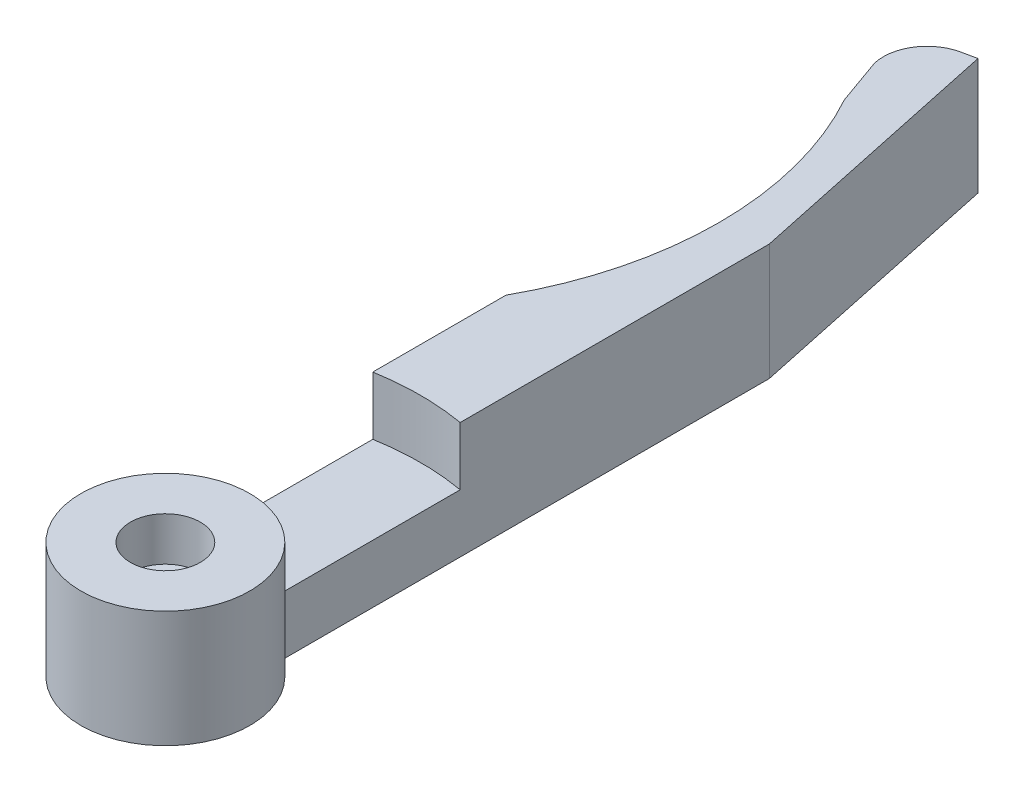
SolidWorks part; units mm, degrees
ref_plane "Plan de face" through (0, 0, 0) normal (0, 0, 1) x (1, 0, 0)
ref_plane "Plan de dessus" through (0, 0, 0) normal (0, 1, 0) x (1, 0, 0)
ref_plane "Plan de droite" through (0, 0, 0) normal (1, 0, 0) x (0, 0, -1)
sketch "Esquisse1" plane through (0, 0, 0) normal (0, 1, 0) x (1, 0, 0)
  line L0 (-3, 50.619) -> (-3, 49.619) construction
  line L1 (2, 55.619) -> (3, 55.619) construction
  line L2 (-3, 55.619) -> (-3, 4.9639) construction
  line L3 (-3, 4.9639) -> (3, 4.9639) construction
  line L4 (3, 55.619) -> (3, 4.9639) construction
  line L5 (-3, 26.381) -> (-3, 4.9639)
  line L7 (-3, 4.9639) -> (3, 4.9639) construction
  line L12 (0, 4.9639) -> (0, -14.5149) construction
  line L13 (-4.1404, 52.822) -> (-3, 49.619)
  line L14 (-1.8453, 56.4495) -> (-0.8672, 56.6574)
  line L15 (-0.8672, 56.6574) -> (3, 38.4639)
  line L16 (3, 38.4639) -> (3, 4.9639)
  arc A0 (-3, 49.619) -> (-3, 26.381) centre (-24, 38) cw
  arc A1 (2, 55.619) -> (-3, 50.619) centre (2, 50.619) ccw construction
  circle A2 centre (0, 0) radius 2.4 construction
  arc A3 (-4.1404, 52.822) -> (-1.8453, 56.4495) centre (-1.2216, 53.5151) cw
  arc A4 (-3, 4.9639) -> (3, 4.9639) centre (0, 0) ccw
  point P19 (0, 38)
  point P25 (-4.3024, 55.9871)
  dimension "D2" = 24
  dimension "D5" = 5
  dimension "D10" = 3
  dimension "D7" = 4.8
  dimension "D11" = 5.8
  dimension "D1" = 6
  dimension "D3" = 21
  dimension "D4" = 6
  dimension "D6" = 38
  dimension "D8" = 3.5
  dimension "D9" = 6.5
  dimension "D12" = 33.5
  dimension "D13" = 12
  dimension "D14" = 18.6
  dimension "D15" = 3.4
  dimension "D16" = 1
extrude "Boss.-Extru.1" add sketch "Esquisse1" along normal blind 8
sketch "Esquisse2" plane through (0, 8, 0) normal (0, 1, 0) x (1, 0, 0)
  line L0 (0, 38) -> (0, 0) construction
  circle A0 centre (0, 0) radius 2.4
  arc A1 (-3, 26.381) -> (-3, 49.619) centre (-24, 38) ccw construction
  dimension "D2" = 4.8
  dimension "D1" = 38
extrude "Enlèv. mat.-Extru.1" cut sketch "Esquisse2" against normal blind 3
sketch "Esquisse3" plane through (0, 5, 0) normal (0, 1, 0) x (1, 0, 0)
  circle A0 centre (0, 0) radius 1.25
  dimension "D1" = 2.5
extrude "Enlèv. mat.-Extru.2" cut sketch "Esquisse3" against normal up to next
sketch "Esquisse4" plane through (0, 0, 0) normal (0, -1, 0) x (1, 0, 0)
  circle A0 centre (0, 0) radius 3
  dimension "D1" = 6
extrude "Enlèv. mat.-Extru.3" cut sketch "Esquisse4" against normal blind 2
sketch "Esquisse5" plane through (0, 8, 0) normal (0, 1, 0) x (1, 0, 0)
  line L0 (-3, 4.9639) -> (-3, 17.2409)
  line L1 (3, 4.9639) -> (3, 17.2409)
  line L2 (3, 4.9639) -> (3, 38.4639) construction
  circle A0 centre (0, 0) radius 5.8 construction
  circle A1 centre (0, 0) radius 17.5 construction
  arc A2 (-3, 4.9639) -> (3, 4.9639) centre (0, 0) ccw construction
  arc A3 (-3, 4.9639) -> (3, 4.9639) centre (0, 0) cw
  arc A4 (-3, 17.2409) -> (3, 17.2409) centre (0, 0) cw
  dimension "D1" = 35
extrude "Enlèv. mat.-Extru.4" cut sketch "Esquisse5" against normal blind 4
